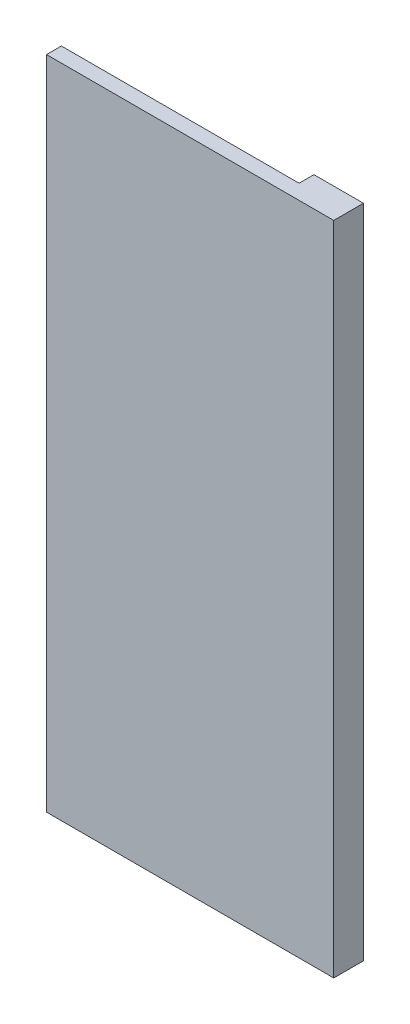
SolidWorks part; units mm, degrees
ref_plane "Front Plane" through (0, 0, 0) normal (0, 0, 1) x (1, 0, 0)
ref_plane "Top Plane" through (0, 0, 0) normal (0, 1, 0) x (1, 0, 0)
ref_plane "Right Plane" through (0, 0, 0) normal (1, 0, 0) x (0, 0, -1)
sketch "Sketch1" plane through (0, 0, 0) normal (0, 0, 1) x (1, 0, 0)
  line L1 (-48, 245) -> (68, 245)
  line L2 (-48, 245) -> (-48, -20)
  line L3 (-48, -20) -> (68, -20)
  line L4 (68, 245) -> (68, -20)
  line L5 (-48, 245) -> (48, 245)
  line L6 (-48, 245) -> (-48, 0)
  line L7 (-48, 0) -> (48, 0)
  line L8 (48, 245) -> (48, 0)
  dimension "D1" = 20
  dimension "D2" = 20
extrude "Boss-Extrude1" add sketch "Sketch1" against normal blind 6 contours L1 L8 L7 L2 L3 L4 region at (58, 242.1072, 0)
sketch "Sketch2" plane through (0, 0, 0) normal (0, 0, 1) x (1, 0, 0)
  line L1 (68, -20) -> (-48, -20)
  line L2 (68, -20) -> (68, 245)
  line L3 (68, 245) -> (-48, 245)
  line L4 (-48, -20) -> (-48, 245)
extrude "Boss-Extrude2" add sketch "Sketch2" along normal blind 6
